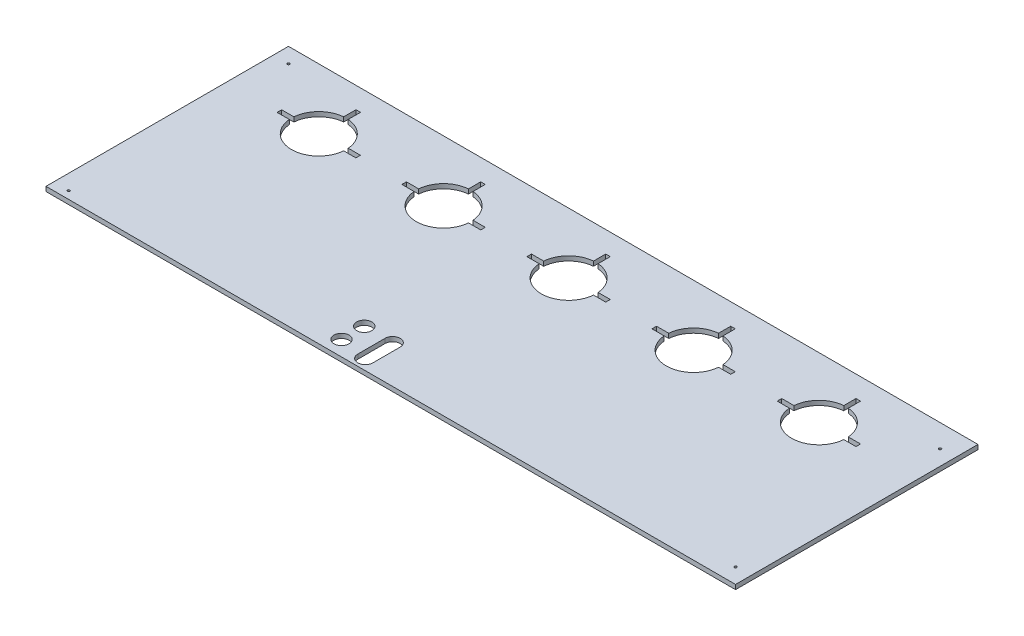
SolidWorks part; units mm, degrees
ref_plane "Front Plane" through (0, 0, 0) normal (0, 0, 1) x (1, 0, 0)
ref_plane "Top Plane" through (0, 0, 0) normal (0, 1, 0) x (1, 0, 0)
ref_plane "Right Plane" through (0, 0, 0) normal (1, 0, 0) x (0, 0, -1)
sketch "Sketch1" plane through (0, 0, 0) normal (0, 1, 0) x (1, 0, 0)
  line L1 (-227.5, -80) -> (227.5, -80)
  line L2 (-227.5, -80) -> (-227.5, 80)
  line L3 (-227.5, 80) -> (227.5, 80)
  line L4 (227.5, -80) -> (227.5, 80)
  line L5 (-227.5, -80) -> (227.5, 80) construction
  line L6 (-227.5, 80) -> (227.5, -80) construction
  point P0 (0, 0)
  dimension "D1" = 455
  dimension "D2" = 160
extrude "Boss-Extrude1" add sketch "Sketch1" along normal blind 3
sketch "Sketch2" plane through (0, 3, 0) normal (0, 1, 0) x (1, 0, 0)
  line L0 (227.5, 80) -> (-227.5, 80) construction
  line L1 (-227.5, 80) -> (-227.5, -80) construction
  line L2 (227.5, -80) -> (227.5, 80) construction
  line L3 (-227.5, -80) -> (227.5, -80) construction
  line L4 (-28.778, -55) -> (-28.778, -73)
  line L5 (-18.778, -55) -> (-18.778, -73)
  circle A0 centre (-167.5, 40) radius 18
  circle A1 centre (-85.1511, 40) radius 18
  circle A2 centre (-2.6511, 40) radius 18
  circle A3 centre (79.8489, 40) radius 18
  circle A4 centre (162.5, 40) radius 18
  circle A5 centre (-42.5, -55) radius 5
  circle A6 centre (-42.5, -70) radius 5
  arc A7 (-28.778, -55) -> (-18.778, -55) centre (-23.778, -55) cw
  arc A8 (-28.778, -73) -> (-18.778, -73) centre (-23.778, -73) ccw
  dimension "D1" = 36
  dimension "D4" = 36
  dimension "D5" = 36
  dimension "D6" = 36
  dimension "D7" = 36
  dimension "D12" = 10
  dimension "D18" = 10
  dimension "D3" = 60
  dimension "D8" = 82.5
  dimension "D9" = 65
  dimension "D10" = 82.5
  dimension "D11" = 40
  dimension "D13" = 185
  dimension "D14" = 25
  dimension "D19" = 15
  dimension "D20" = 40
  dimension "D21" = 40
  dimension "D22" = 40
  dimension "D23" = 40
extrude "Cut-Extrude1" cut sketch "Sketch2" against normal blind 3
hole_wizard "1/16 (0.0625) Diameter Hole2" positions "Sketch6" profile "Sketch5" hole size "1/16" standard "ANSI Inch" end condition through all
sketch "Sketch6" plane through (0, 3, 0) normal (0, 1, 0) x (1, 0, 0)
  line L0 (-227.5, -80) -> (227.5, -80) construction
  line L1 (-227.5, 80) -> (-227.5, -80) construction
  line L2 (227.5, 80) -> (-227.5, 80) construction
  line L3 (227.5, -80) -> (227.5, 80) construction
  point P0 (-217.5, -75)
  point P2 (-217.5, 70)
  point P11 (217.5, -70)
  point P13 (217.5, 65)
  dimension "D1" = 5
  dimension "D2" = 10
  dimension "D3" = 10
  dimension "D4" = 10
  dimension "D5" = 10
  dimension "D6" = 10
sketch "Sketch5" plane through (-217.5, 3, 75) normal (1, 0, 0) x (0, 0, 1)
  line L0 (0, 0) -> (0, 3)
  line L1 (0, 3) -> (0.7937, 3)
  line L2 (0.7937, 3) -> (0.7937, 0)
  line L5 (0.7937, 0) -> (0, 0)
  line L11 (0, -6.35) -> (0, 107.95) construction
  dimension "Thru Hole Dia." = 1.5875
  dimension "Thru Hole Depth" = 3
sketch "Sketch7" plane through (0, 3, 0) normal (0, 1, 0) x (1, 0, 0)
  line L1 (-141.5, 38.5) -> (-193.5, 38.5)
  line L2 (-141.5, 38.5) -> (-141.5, 41.5)
  line L3 (-141.5, 41.5) -> (-193.5, 41.5)
  line L4 (-193.5, 38.5) -> (-193.5, 41.5)
  line L5 (-141.5, 38.5) -> (-193.5, 41.5) construction
  line L6 (-141.5, 41.5) -> (-193.5, 38.5) construction
  line L7 (-169.0222, 40.0878) -> (-166.0222, 40.0878)
  line L8 (-169.0222, 40.0878) -> (-169.0222, 66.0865)
  line L9 (-169.0222, 66.0865) -> (-166.0222, 66.0865)
  line L10 (-166.0222, 40.0878) -> (-166.0222, 66.0865)
  line L11 (-111.1511, 38.5) -> (-59.1511, 38.5)
  line L12 (-111.1511, 38.5) -> (-111.1511, 41.5)
  line L13 (-111.1511, 41.5) -> (-59.1511, 41.5)
  line L14 (-59.1511, 38.5) -> (-59.1511, 41.5)
  line L15 (-111.1511, 38.5) -> (-59.1511, 41.5) construction
  line L16 (-111.1511, 41.5) -> (-59.1511, 38.5) construction
  line L17 (105.8489, 38.5) -> (53.8489, 38.5)
  line L18 (105.8489, 38.5) -> (105.8489, 41.5)
  line L19 (105.8489, 41.5) -> (53.8489, 41.5)
  line L20 (53.8489, 38.5) -> (53.8489, 41.5)
  line L21 (105.8489, 38.5) -> (53.8489, 41.5) construction
  line L22 (105.8489, 41.5) -> (53.8489, 38.5) construction
  line L23 (188.5, 38.5) -> (136.5, 38.5)
  line L24 (188.5, 38.5) -> (188.5, 41.5)
  line L25 (188.5, 41.5) -> (136.5, 41.5)
  line L26 (136.5, 38.5) -> (136.5, 41.5)
  line L27 (188.5, 38.5) -> (136.5, 41.5) construction
  line L28 (188.5, 41.5) -> (136.5, 38.5) construction
  line L29 (23.3489, 38.5) -> (-28.6511, 38.5)
  line L30 (23.3489, 38.5) -> (23.3489, 41.5)
  line L31 (23.3489, 41.5) -> (-28.6511, 41.5)
  line L32 (-28.6511, 38.5) -> (-28.6511, 41.5)
  line L33 (23.3489, 38.5) -> (-28.6511, 41.5) construction
  line L34 (23.3489, 41.5) -> (-28.6511, 38.5) construction
  line L35 (-86.6511, 66) -> (-83.6511, 66)
  line L36 (-86.6511, 66) -> (-86.6511, 40)
  line L37 (-91.21, 38.5) -> (-86.4871, 38.5)
  line L38 (-86.6511, 40) -> (-83.6511, 40)
  line L39 (-4.1511, 66) -> (-1.1511, 66)
  line L40 (-4.1511, 66) -> (-4.1511, 40)
  line L41 (-4.1511, 40) -> (-1.1511, 40)
  line L42 (-1.1511, 66) -> (-1.1511, 40)
  line L43 (78.3489, 66) -> (81.3489, 66)
  line L44 (78.3489, 66) -> (78.3489, 40)
  line L45 (78.3489, 40) -> (81.3489, 40)
  line L46 (81.3489, 66) -> (81.3489, 40)
  line L47 (161, 66) -> (164, 66)
  line L48 (161, 66) -> (161, 40)
  line L49 (161, 40) -> (164, 40)
  line L50 (164, 66) -> (164, 40)
  line L51 (-83.6511, 66) -> (-83.6511, 40)
  point P0 (-167.5, 40)
  point P10 (-85.1511, 40)
  point P16 (79.8489, 40)
  point P22 (162.5, 40)
  point P28 (-2.6511, 40)
  circle M7 centre (162.5, 40) radius 18
  circle M8 centre (79.8489, 40) radius 18
  circle M9 centre (-2.6511, 40) radius 18
  circle M10 centre (-85.1511, 40) radius 18
  circle M11 centre (-167.5, 40) radius 18
  dimension "D1" = 3
  dimension "D2" = 52
  dimension "D3" = 0.0878
  dimension "D4" = 0
  dimension "D5" = 0
  dimension "D6" = 52
  dimension "D7" = 3
  dimension "D8" = 52
  dimension "D9" = 3
  dimension "D10" = 52
  dimension "D11" = 3
  dimension "D12" = 52
  dimension "D13" = 3
  dimension "D14" = 1.5
  dimension "D15" = 1.5
  dimension "D16" = 3
  dimension "D17" = 26
  dimension "D18" = 26
  dimension "D19" = 0
  dimension "D20" = 1.5
  dimension "D21" = 3
  dimension "D22" = 26
  dimension "D23" = 1.5
  dimension "D24" = 3
  dimension "D25" = 26
  dimension "D26" = 0
  dimension "D27" = 3
extrude "Cut-Extrude2" cut sketch "Sketch7" against normal blind 10 contours L10 L9 L8 M11 | L2 L3 L1 M11 | L4 L1 L3 M11 region at (-145.5104, 3, -40) region at (-189.4896, 3, -40) region at (-167.5223, 3, -62.0328)
extrude "Cut-Extrude3" cut sketch "Sketch7<4>" against normal blind 10 contours L11 L14 L13 M10 | L13 L12 L11 M10 | L51 L35 L36 M10 | L42 L39 L40 M9 | L30 L31 L29 M9 | L32 L29 L31 M9 | L46 L43 L44 M8 | L18 L19 L17 M8 | L20 L17 L19 M8 | L26 L23 L25 M7 | L50 L47 L48 M7 | L24 L25 L23 M7 | L36 L38 L51 L35 region at (-107.1407, 3, -40) region at (-63.1615, 3, -40) region at (-85.1511, 3, -61.9896) region at (101.8385, 3, -40) region at (57.8593, 3, -40) region at (79.8489, 3, -61.9895) region at (184.4896, 3, -40) region at (140.5104, 3, -40) region at (162.5, 3, -61.9896) region at (19.3385, 3, -40) region at (-24.6407, 3, -40) region at (-2.6511, 3, -61.9896)
sketch "Sketch7<4>" plane through (0, 3, 0) normal (0, 1, 0) x (1, 0, 0) same geometry as "Sketch7"
